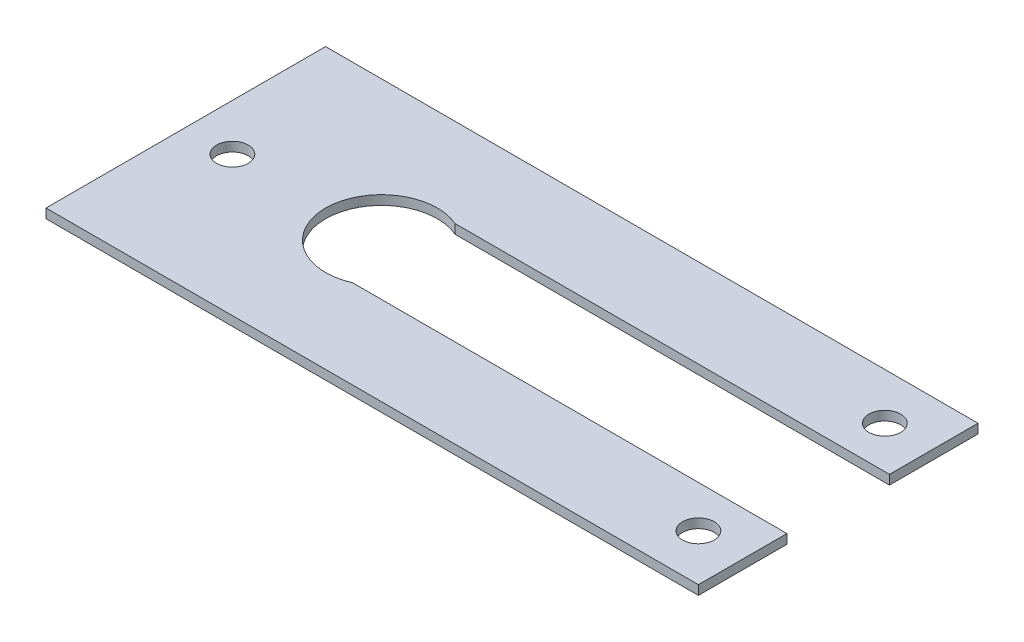
SolidWorks part; units mm, degrees
ref_plane "Plan de face" through (0, 0, 0) normal (0, 0, 1) x (1, 0, 0)
ref_plane "Plan de dessus" through (0, 0, 0) normal (0, 1, 0) x (1, 0, 0)
ref_plane "Plan de droite" through (0, 0, 0) normal (1, 0, 0) x (0, 0, -1)
sketch "Esquisse1" plane through (0, 0, 0) normal (0, 1, 0) x (1, 0, 0)
  line L0 (-0.55, 0) -> (0.55, 0) construction
  line L1 (-35, -15) -> (35, -15)
  line L2 (-35, -15) -> (-35, 15)
  line L3 (-35, 15) -> (35, 15)
  line L4 (35, -15) -> (35, -5.5)
  line L5 (-35, -15) -> (35, 15) construction
  line L6 (-35, 15) -> (35, -15) construction
  line L7 (-11.6021, 5.5) -> (35, 5.5)
  line L8 (-11.6021, -5.5) -> (35, -5.5)
  line L9 (35, 5.5) -> (35, 15)
  arc A0 (-11.6021, 5.5) -> (-11.6021, -5.5) centre (-14, 0) ccw
  circle A1 centre (30, 10) radius 1.7
  circle A3 centre (30, -10) radius 1.7
  circle A4 centre (-30, 0) radius 1.7
  point P0 (0, 0)
  dimension "D3" = 12
  dimension "D4" = 49
  dimension "D6" = 3.4
  dimension "D7" = 5
  dimension "D9" = 3.4
  dimension "D1" = 30
  dimension "D2" = 70
  dimension "D5" = 11
  dimension "D8" = 5
  dimension "D10" = 5
base flange "Tôle de base pliée1" sketch "Esquisse1" thickness 1 reverse thickness direction no parameters "D1"=0.7366
sketch "Esquisse13" plane through (0, 0, 0) normal (0, 0, 1) x (1, 0, 0)
  line L0 (-20, 0) -> (-20, -1) construction
sketch "Lignes de pliage3" [suppressed] plane through (0, 0, 0) normal (0, 1, 0) x (1, 0, 0)
sketch "Cube de visualisation3" [suppressed] plane through (0, 0, 0) normal (0, 1, 0) x (1, 0, 0)
sheet metal parameters "Tôlerie3" thickness 1 parameters "D1"=0.7366
flat pattern "Etat déplié3" [suppressed]
sketch "Lignes de pliage4" plane through (0, 0, 0) normal (0, 1, 0) x (1, 0, 0)
sketch3d "Cube de visualisation4" [suppressed]
  line L0 (49, -15, 0) -> (-21, -15, 0) construction
  line L1 (49, 15, 0) -> (-21, 15, 0) construction
  line L2 (49, -15, 0) -> (49, 15, 0) construction
  line L3 (-21, -15, 0) -> (-21, 15, 0) construction
